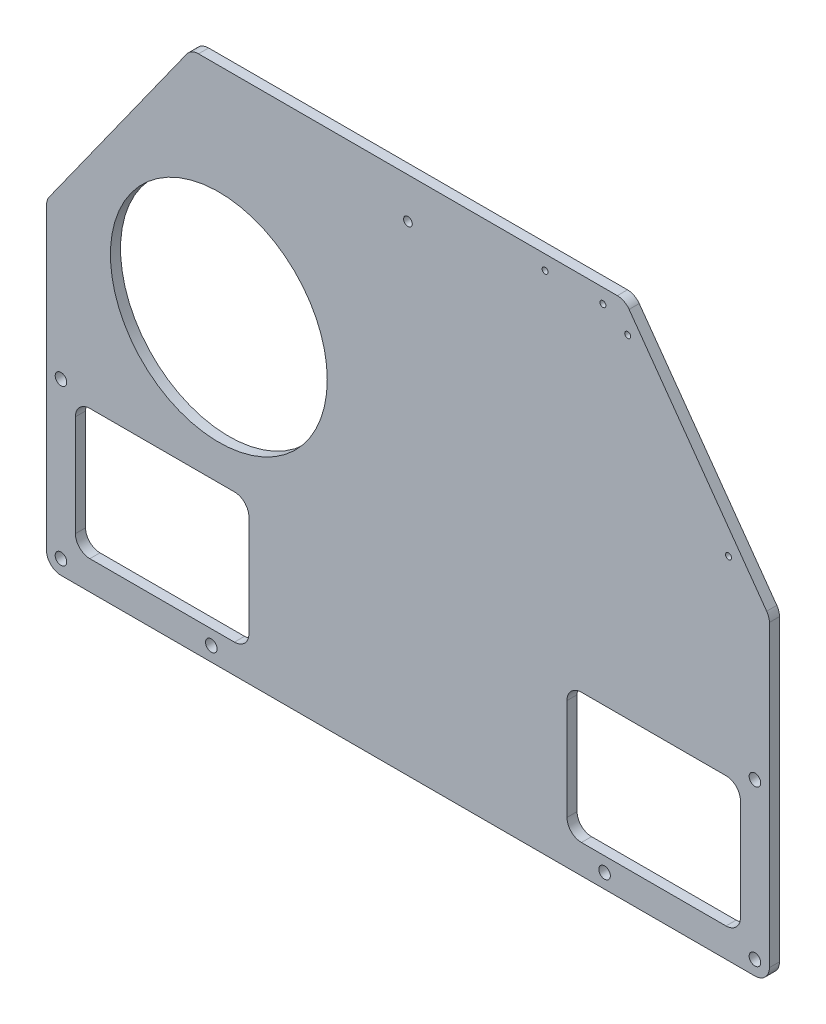
SolidWorks part; units mm, degrees
ref_plane "Plan de face" through (0, 0, 0) normal (0, 0, 1) x (1, 0, 0)
ref_plane "Plan de dessus" through (0, 0, 0) normal (0, 1, 0) x (1, 0, 0)
ref_plane "Plan de droite" through (0, 0, 0) normal (1, 0, 0) x (0, 0, -1)
sketch "Esquisse1" plane through (0, 0, 0) normal (0, 0, 1) x (1, 0, 0)
  line L1 (5, 0) -> (245, 0)
  line L2 (0, 5) -> (0, 305)
  line L3 (0, 305) -> (250, 305)
  line L4 (250, 5) -> (250, 305)
  arc A0 (250, 5) -> (245, 0) centre (245, 5) cw
  arc A1 (5, 0) -> (0, 5) centre (5, 5) cw
  point P7 (250, 0)
  point P10 (0, 0)
  dimension "D2" = 5
  dimension "D3" = 5
  dimension "D1" = 250
  dimension "D4" = 300
extrude "Boss.-Extru.1" add sketch "Esquisse1" along normal blind 3.5
sketch "Esquisse2" plane through (0, 0, 3.5) normal (0, 0, 1) x (1, 0, 0)
  line L0 (-19.0099, 5) -> (402.2953, 5) construction
  line L1 (5, 0) -> (245, 0) construction
  line L2 (5, -25.1291) -> (5, 139.966) construction
  line L3 (0, 305) -> (0, 5) construction
  line L4 (245, -22.1166) -> (245, 94.5536) construction
  line L5 (250, 5) -> (250, 305) construction
  line L6 (-9.3926, 58.8) -> (267.0784, 58.8) construction
  circle A0 centre (5, 5) radius 2
  circle A1 centre (245, 5) radius 2
  circle A2 centre (5, 58.8) radius 2
  circle A3 centre (245, 58.8) radius 2
  dimension "D1" = 4
  dimension "D2" = 4
  dimension "D7" = 4
  dimension "D8" = 4
  dimension "D3" = 5
  dimension "D4" = 5
  dimension "D5" = 5
  dimension "D6" = 53.8
extrude "Enlèv. mat.-Extru.1" cut sketch "Esquisse2" against normal through all
sketch "Esquisse3" plane through (0, 0, 3.5) normal (0, 0, 1) x (1, 0, 0)
  line L0 (-13.1091, 5) -> (277.0265, 5) construction
  line L1 (5, 0) -> (245, 0) construction
  line L2 (0, 305) -> (0, 5) construction
  circle A0 centre (57, 5) radius 2
  circle A1 centre (193, 5) radius 2
  dimension "D3" = 4
  dimension "D4" = 4
  dimension "D1" = 5
  dimension "D2" = 136
  dimension "D5" = 57
extrude "Enlèv. mat.-Extru.2" cut sketch "Esquisse3" against normal through all
sketch "Esquisse4" plane through (0, 0, 0) normal (0, 0, -1) x (-1, 0, 0)
  line L0 (-70, 15) -> (-70, 50)
  line L1 (-65, 55) -> (-15, 55)
  line L2 (-10, 50) -> (-10, 15)
  line L3 (-15, 10) -> (-65, 10)
  line L4 (-5, 0) -> (-245, 0) construction
  line L5 (0, 305) -> (0, 5) construction
  line L6 (-185, 10) -> (-235, 10)
  line L7 (-180, 15) -> (-180, 50)
  line L8 (-185, 55) -> (-235, 55)
  line L9 (-240, 15) -> (-240, 50)
  line L10 (-250, 5) -> (-250, 305) construction
  arc A0 (-70, 50) -> (-65, 55) centre (-65, 50) cw
  arc A1 (-15, 55) -> (-10, 50) centre (-15, 50) cw
  arc A2 (-70, 15) -> (-65, 10) centre (-65, 15) ccw
  arc A3 (-10, 15) -> (-15, 10) centre (-15, 15) cw
  arc A4 (-240, 50) -> (-235, 55) centre (-235, 50) cw
  arc A5 (-180, 50) -> (-185, 55) centre (-185, 50) ccw
  arc A6 (-240, 15) -> (-235, 10) centre (-235, 15) ccw
  arc A7 (-185, 10) -> (-180, 15) centre (-185, 15) ccw
  point P9 (-70, 55)
  point P12 (-10, 55)
  point P18 (-10, 10)
  point P27 (-240, 55)
  point P30 (-180, 55)
  point P35 (-180, 10)
  dimension "D4" = 5
  dimension "D10" = 5
  dimension "D1" = 10
  dimension "D2" = 60
  dimension "D3" = 45
  dimension "D5" = 10
  dimension "D6" = 10
  dimension "D7" = 45
  dimension "D8" = 60
  dimension "D9" = 10
extrude "Enlèv. mat.-Extru.3" cut sketch "Esquisse4" against normal through all
sketch "Esquisse5" plane through (0, 0, 3.5) normal (0, 0, 1) x (1, 0, 0)
  line L0 (0, 110) -> (50, 180)
  line L2 (50, 180) -> (200, 180)
  line L3 (200, 180) -> (250, 110)
  line L5 (125, 623.6506) -> (125, -13.6506) construction
  line L6 (250, 305) -> (0, 305) construction
  line L7 (5, 0) -> (245, 0) construction
  point P12 (125, 305)
  point P13 (125, 180)
  dimension "D1" = 150
  dimension "D2" = 180
  dimension "D3" = 110
  dimension "D4" = 110
extrude "Enlèv. mat.-Extru.4" cut sketch "Esquisse5" against normal through all and the other way through all
sketch "Esquisse6" plane through (0, 0, 3.5) normal (0, 0, 1) x (1, 0, 0)
  line L0 (50, 180) -> (200, 180) construction
  line L4 (125, 209.3374) -> (125, 98.3712) construction
  circle A0 centre (125, 166) radius 1.5
  dimension "D3" = 3
  dimension "D1" = 14
  dimension "D4" = 75
extrude "Enlèv. mat.-Extru.5" cut sketch "Esquisse6" against normal through all
fillet "Congé1" radius 5 4 edges at (250, 110, 1.75) (200, 180, 1.75) (50, 180, 1.75) (0, 110, 1.75)
sketch "Esquisse7" plane through (0, 0, 3.5) normal (0, 0, 1) x (1, 0, 0)
  line L0 (0, 108.3977) -> (0, 5) construction
  line L1 (0.9313, 111.3039) -> (48.5044, 177.9062) construction
  circle A0 centre (59.6, 104.6468) radius 37.5
  dimension "D3" = 75
  dimension "D1" = 59.6
  dimension "D2" = 51.61
extrude "Enlèv. mat.-Extru.6" cut sketch "Esquisse7" against normal through all
sketch "Esquisse8" plane through (0, 0, 3.5) normal (0, 0, 1) x (1, 0, 0)
  line L0 (52.5731, 180) -> (197.4269, 180) construction
  line L1 (201.4956, 177.9062) -> (249.0687, 111.3039) construction
  circle A0 centre (192.4269, 175) radius 1.025
  circle A1 centre (172.4269, 175) radius 1.025
  arc A2 (201.4956, 177.9062) -> (197.4269, 180) centre (197.4269, 175) ccw construction
  circle A3 centre (235.8726, 121.176) radius 1.025
  circle A4 centre (200.9983, 170) radius 1.025
  dimension "D1" = 20
  dimension "D2" = 2.05
  dimension "D3" = 2.05
  dimension "D6" = 2.05
  dimension "D7" = 2.05
  dimension "D10" = 60
  dimension "D11" = 10
  dimension "D4" = 5
  dimension "D5" = 5
  dimension "D8" = 5
  dimension "D9" = 5
extrude "Enlèv. mat.-Extru.7" cut sketch "Esquisse8" against normal through all
